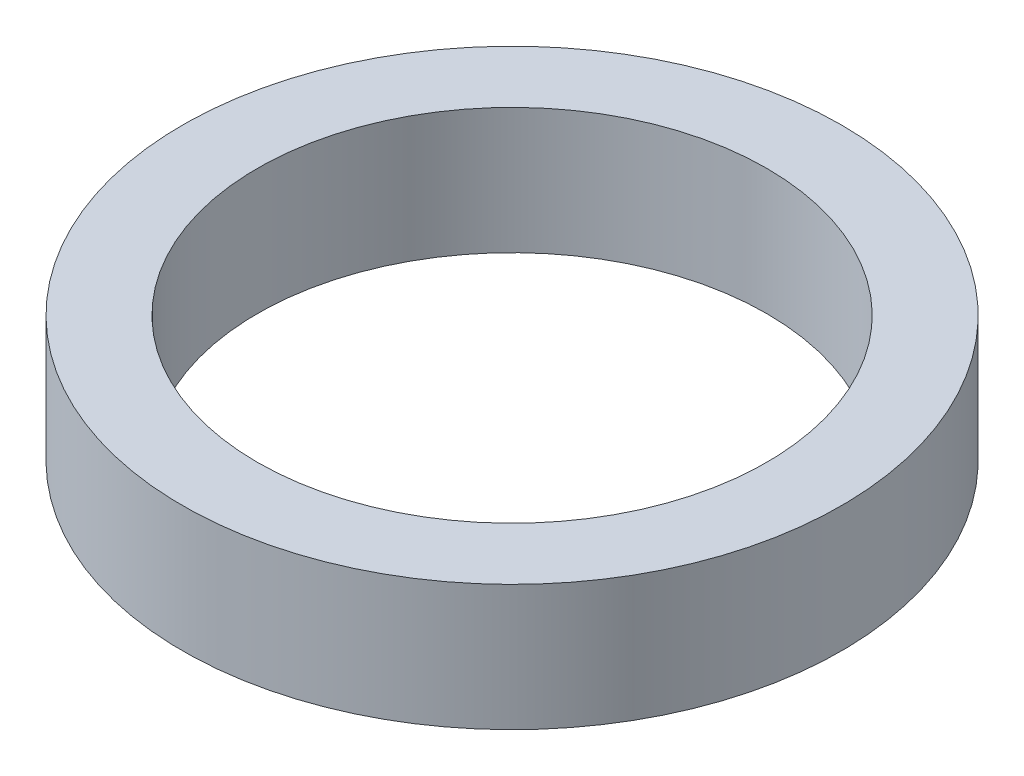
SolidWorks part; units mm, degrees
ref_plane "Front Plane" through (0, 0, 0) normal (0, 0, 1) x (1, 0, 0)
ref_plane "Top Plane" through (0, 0, 0) normal (0, 1, 0) x (1, 0, 0)
ref_plane "Right Plane" through (0, 0, 0) normal (1, 0, 0) x (0, 0, -1)
sketch "Sketch1" plane through (0, 0, 0) normal (0, 1, 0) x (1, 0, 0)
  circle A0 centre (0, 0) radius 55
  dimension "FLANGE_OD" = 110
extrude "Boss-Extrude1" add sketch "Sketch1" along normal blind 21
sketch "Sketch2" plane through (0, 0, 0) normal (0, 1, 0) x (1, 0, 0)
  circle A0 centre (0, 0) radius 42.5
  dimension "BORE_D" = 85
extrude "Cut-Extrude1" cut sketch "Sketch2" along normal through all
sketch "Sketch3" plane through (0, 21, 0) normal (0, 1, 0) x (1, 0, 0)
  circle A0 centre (0, 0) radius 23.228 construction
  circle A1 centre (-23.228, 0) radius 1.9768
  dimension "BOLT_D" = 3.9536
  dimension "BOLT_PCD" = 46.456
extrude "Cut-Extrude2" cut sketch "Sketch3" against normal blind 15.1053 rebuild error yes
pattern_circular "CirPattern1" count 6 over 360 rebuild error yes
